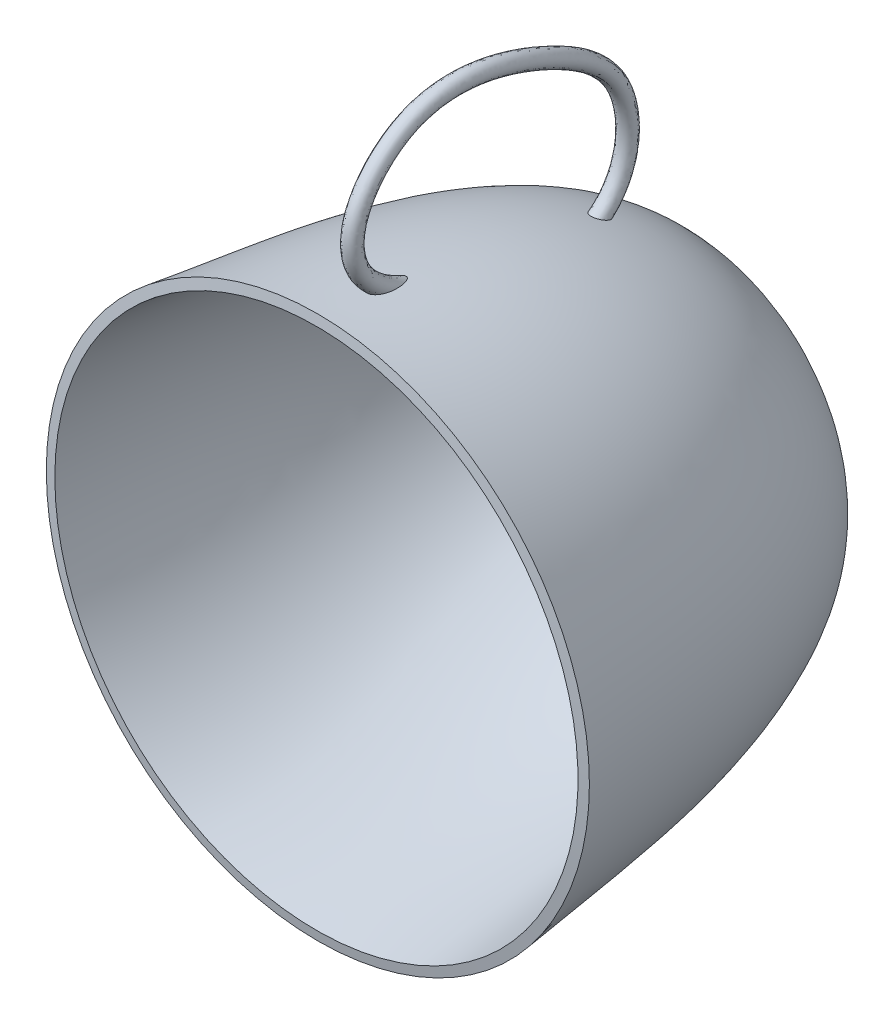
SolidWorks part; units mm, degrees
ref_plane "Front Plane" through (0, 0, 0) normal (1, 0, 0) x (0, 1, 0)
ref_plane "Top Plane" through (0, 0, 0) normal (0, 0, 1) x (0, 1, 0)
ref_plane "Right Plane" through (0, 0, 0) normal (0, 1, 0) x (-1, 0, 0)
sketch "Sketch1" plane through (0, 0, 0) normal (1, 0, 0) x (0, 1, 0)
  line L0 (0, 0) -> (35.5895, 0)
  line L1 (0, 3) -> (35.0181, 3)
  line L2 (0, 0) -> (0, 3)
  line L3 (80.99, 117.6203) -> (78.0207, 118.0487)
  line L4 (0, 3) -> (0, 150.9839) construction
  spline S0 degree 3 poles (35.5895, 0) (50.4615, 5.7538) (63.0133, 26.3381) (75.6363, 68.1732) (78.0495, 97.242) (80.99, 117.6203) knots 0 0 0 0 0.339604 0.527678 1 1 1 1
  spline S1 degree 1 poles (35.0181, 3) (78.0207, 118.0487) knots 0 0 1 1 construction
  spline S2 degree 3 poles (35.0181, 3) (35.635, 3.2492) (36.8638, 3.7849) (39.1943, 4.9558) (41.9307, 6.6195) (44.9434, 8.907) (48.6366, 12.3187) (52.6938, 17.2059) (56.8011, 23.8592) (60.2678, 31.0705) (64.2277, 41.0546) (68.0809, 53.8186) (71.3884, 69.5693) (74.6415, 90.9489) (76.4644, 107.2629) (78.0207, 118.0487) knots 0.004228 0.004228 0.004228 0.004228 0.019787 0.035346 0.066464 0.097581 0.128699 0.190935 0.253171 0.315407 0.377642 0.502114 0.626585 0.751057 1 1 1 1
  dimension "D1" = 3
revolve "Revolve1" add sketch "Sketch1" angle 360 about L4
sketch "Sketch2" plane through (0, 0, 0) normal (1, 0, 0) x (0, 1, 0)
  spline S0 degree 3 poles (74.9262, 91.5165) (85.488, 116.9855) (127.5628, 98.7948) (117.1503, 53.1911) (96.6165, 21.82) (69.6223, 24.1195) (62.3928, 36.2693) knots 0 0 0 0 0.317055 0.598288 0.764367 1 1 1 1
  point P2 (77.7187, 92.6242)
  point P4 (0, 0)
  point P6 (76.4746, 93.3723)
  point P8 (74.9262, 91.5165)
sweep "Sweep1" add path "Sketch2" circular profile diameter 5 parameters "D3"=5
